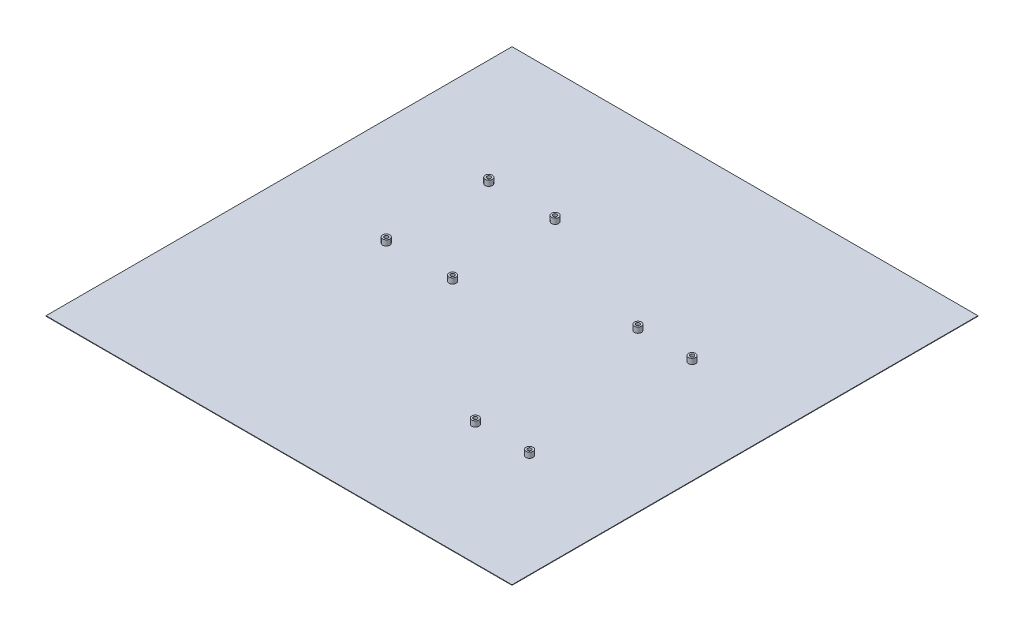
SolidWorks part; units mm, degrees
ref_plane "Front Plane" through (0, 0, 0) normal (0, 0, 1) x (1, 0, 0)
ref_plane "Top Plane" through (0, 0, 0) normal (0, 1, 0) x (1, 0, 0)
ref_plane "Right Plane" through (0, 0, 0) normal (1, 0, 0) x (0, 0, -1)
sketch "Sketch1" plane through (0, 0, 0) normal (0, 1, 0) x (1, 0, 0)
  line L1 (-215, -215) -> (215, -215)
  line L2 (-215, -215) -> (-215, 215)
  line L3 (-215, 215) -> (215, 215)
  line L4 (215, -215) -> (215, 215)
  line L5 (-215, -215) -> (215, 215) construction
  line L6 (-215, 215) -> (215, -215) construction
  point P0 (0, 0)
  dimension "D1" = 430
  dimension "D2" = 430
extrude "Boss-Extrude1" add sketch "Sketch1" along normal blind 0.45
sketch "Sketch6" plane through (0, 0.45, 0) normal (0, 1, 0) x (1, 0, 0)
  circle A0 centre (119.7933, 46.3731) radius 3.3
  circle A1 centre (69.7933, 46.3731) radius 3.3
  circle A2 centre (119.7933, -103.6269) radius 3.3
  circle A3 centre (69.7933, -103.6269) radius 3.3
  point P2 (43, -93)
  point P5 (69.7933, -103.6269)
  point P8 (0, 0)
  point P11 (119.7933, -103.6269)
  point P12 (0, 0)
  point P13 (119.7933, 46.3731)
  point P14 (0, 0)
  point P15 (69.7933, 46.3731)
sketch "Sketch7" plane through (0, 0.45, 0) normal (0, 1, 0) x (1, 0, 0)
  circle A0 centre (-116.3627, 94.9459) radius 3.3
  circle A1 centre (-55.3632, 95.1916) radius 3.3
  circle A2 centre (-54.9804, 0.1924) radius 3.3
  circle A3 centre (-115.98, -0.0534) radius 3.3
extrude "Boss-Extrude2" add sketch "Sketch7" along normal blind 5
sketch "Sketch8" plane through (0, 5.45, 0) normal (0, 1, 0) x (1, 0, 0)
  circle A0 centre (-54.9804, 0.1924) radius 1.75
  circle A1 centre (-55.3632, 95.1916) radius 1.75
  circle A2 centre (-116.3627, 94.9459) radius 1.75
  circle A3 centre (-115.98, -0.0534) radius 1.75
extrude "Cut-Extrude1" cut sketch "Sketch8" against normal blind 4
extrude "Boss-Extrude3" add sketch "Sketch6" along normal blind 5
sketch "Sketch10" plane through (0, 5.45, 0) normal (0, 1, 0) x (1, 0, 0)
  circle A0 centre (69.7933, 46.3731) radius 1.75
  circle A1 centre (119.7933, 46.3731) radius 1.75
  circle A2 centre (119.7933, -103.6269) radius 1.75
  circle A3 centre (69.7933, -103.6269) radius 1.75
extrude "Cut-Extrude2" cut sketch "Sketch10" against normal blind 4
